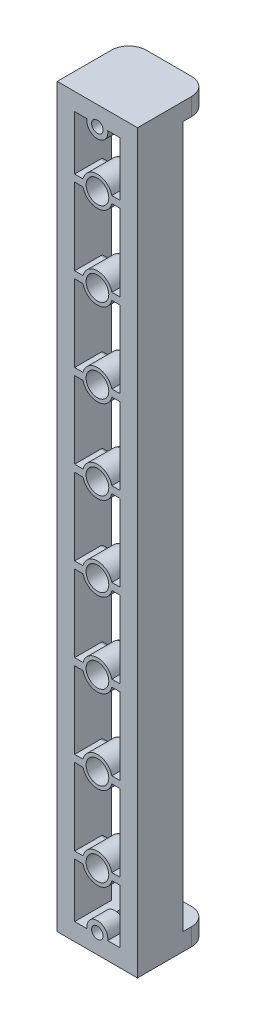
SolidWorks part; units mm, degrees
ref_plane "Front Plane" through (0, 0, 0) normal (0, 0, 1) x (1, 0, 0)
ref_plane "Top Plane" through (0, 0, 0) normal (0, 1, 0) x (1, 0, 0)
ref_plane "Right Plane" through (0, 0, 0) normal (1, 0, 0) x (0, 0, -1)
sketch "Sketch1" plane through (0, 0, 0) normal (0, 0, 1) x (1, 0, 0)
  line L0 (6.5, 100.5) -> (6.5, -100.5)
  line L1 (-11.5, 105.5) -> (11.5, 105.5)
  line L2 (-11.5, 105.5) -> (-11.5, -105.5)
  line L3 (-11.5, -105.5) -> (11.5, -105.5)
  line L4 (11.5, 105.5) -> (11.5, -105.5)
  line L5 (-11.5, 105.5) -> (11.5, -105.5) construction
  line L6 (-11.5, -105.5) -> (11.5, 105.5) construction
  line L7 (-6.5, -100.5) -> (6.5, -100.5)
  line L8 (-6.5, 100.5) -> (-6.5, -100.5)
  line L9 (-6.5, 100.5) -> (6.5, 100.5)
  point P0 (0, 0)
  dimension "D1" = 23
  dimension "D2" = 211
  dimension "D3" = 5
extrude "Boss-Extrude1" add sketch "Sketch1" along normal blind 13
sketch "Sketch7" plane through (0, 0, 13) normal (0, 0, 1) x (1, 0, 0)
  line L0 (0.0237, 87.6593) -> (0.0237, 80.2815) construction
  line L5 (-3.3958, 83) -> (-7.3958, 83)
  line L6 (7.4431, 85) -> (3.4431, 85)
  line L11 (-3.3958, 85) -> (-3.3958, 83)
  line L12 (-7.3958, 85) -> (-3.3958, 85)
  line L13 (3.4431, 85) -> (3.4431, 83)
  line L14 (3.4431, 83) -> (7.4431, 83)
  line L15 (7.4431, 83) -> (7.4431, 85)
  line L16 (-7.3958, 83) -> (-7.3958, 85)
  line L18 (11.5, 105.5) -> (-11.5, 105.5) construction
  circle A0 centre (0.0237, 84) radius 3.25
  circle A1 centre (0.0237, 84) radius 4.25
  point P5 (7.4431, 84)
  dimension "D1" = 6.5
  dimension "D2" = 8.5
  dimension "D3" = 20.5
  dimension "D4" = 4
  dimension "D5" = 2
extrude "Boss-Extrude5" add sketch "Sketch7" against normal blind 8.5
fillet "Fillet4" radius 1 6 edges at (-5.3035, 83, 4.5) (5.3272, 85, 4.5) (-5.3035, 85, 4.5) (0.0237, 88.25, 4.5) (5.3272, 83, 4.5) (0.0237, 79.75, 4.5)
pattern_linear "LPattern7" count 8 spacing 24 along (0, -1, 0) of "Boss-Extrude5", "Fillet4"
sketch "Sketch11" plane through (0, -105.5, 0) normal (0, -1, 0) x (-1, 0, 0)
  line L0 (6.5, -2.0313) -> (6.5, 0)
  line L2 (11.5, 0) -> (-11.5, 0) construction
  line L3 (11.5, -13) -> (11.5, 0) construction
  line L4 (8.5313, 0) -> (6.5, 0)
  line L5 (0, 0) -> (0, -13) construction
  line L6 (11.5, -13) -> (-11.5, -13) construction
  line L7 (-8.5313, 0) -> (-6.5, 0)
  line L8 (-6.5, -2.0313) -> (-6.5, 0)
  arc A0 (6.5, -2.0313) -> (8.5313, 0) centre (6.5, 0) ccw
  arc A1 (-6.5, -2.0313) -> (-8.5313, 0) centre (-6.5, 0) cw
  dimension "D1" = 5
ref_plane "Plane1" through (0, 0, 0) normal (-1, 0, 0) x (0, 0, 1)
ref_plane "Plane2" through (0, 0, 0) normal (0, 1, 0) x (1, 0, 0)
sketch "Sketch15" plane through (0, 105.5, 0) normal (0, 1, 0) x (1, 0, 0)
  line L0 (11.5, 0) -> (-11.5, 0)
  line L4 (11.5, 0) -> (4.4687, 0)
  line L5 (-11.5, 0) -> (-11.5, -13)
  line L6 (-11.5, -13) -> (11.5, -13)
  line L7 (11.5, -13) -> (11.5, 0)
  line L9 (-11.5, 0) -> (-11.5, -13)
  line L10 (-11.5, -13) -> (11.5, -13)
  line L11 (11.5, -13) -> (11.5, 0)
  line L21 (-6.5, 0) -> (-6.5, -2.0313)
  line L25 (-8.5313, 0) -> (-11.5, 0)
  line L26 (6.5, -2.0313) -> (6.5, 0)
  line L27 (6.5, 0) -> (-6.5, 0)
  arc A2 (-8.5313, 0) -> (-6.5, -2.0313) centre (-6.5, 0) ccw
  arc A6 (6.5, -2.0313) -> (4.4687, 0) centre (6.5, 0) ccw
  dimension "D1" = 0
extrude "Boss-Extrude8" add sketch "Sketch15" along normal blind 5
mirror "Mirror5" about plane through (0, 0, 0) normal (0, 1, 0) of "Boss-Extrude8"
sketch "Sketch19" plane through (-11.5, 0, 0) normal (-1, 0, 0) x (0, 0, 1)
  line L0 (13, 105.5) -> (0, 105.5) construction
  line L1 (13, 110.5) -> (13, -110.5) construction
  line L2 (0, 110.5) -> (0, -110.5) construction
  line L3 (0, 110.5) -> (13, 110.5) construction
  line L4 (13, 82.75) -> (0, 82.75) construction
  line L5 (13, 84.75) -> (0, 84.75) construction
  line L6 (0, 98.125) -> (13, 98.125) construction
  line L7 (9.5485, 103.625) -> (3.5485, 103.625)
  line L8 (3.5485, 103.625) -> (3.5485, 98.625)
  line L9 (3.5485, 98.625) -> (9.5485, 103.625)
  line L10 (11.5, 103.625) -> (11.5, 98.625)
  line L11 (11.5, 98.625) -> (5.5, 98.625)
  line L12 (5.5, 98.625) -> (11.5, 103.625)
  line L13 (0, 92.125) -> (13, 92.125) construction
  line L14 (0, 0) -> (13, 0) construction
  line L15 (11.5, 97.625) -> (5.5, 97.625)
  line L16 (11.5, 92.625) -> (11.5, 97.625)
  line L17 (5.5, 97.625) -> (11.5, 92.625)
  line L18 (3.5485, 92.625) -> (3.5485, 97.625)
  line L19 (9.5485, 92.625) -> (3.5485, 92.625)
  line L20 (3.5485, 97.625) -> (9.5485, 92.625)
  line L21 (11.5, 91.625) -> (11.5, 86.625)
  line L22 (5.5, 86.625) -> (11.5, 91.625)
  line L23 (11.5, 86.625) -> (5.5, 86.625)
  line L24 (9.5485, 91.625) -> (3.5485, 91.625)
  line L25 (3.5485, 86.625) -> (9.5485, 91.625)
  line L26 (3.5485, 91.625) -> (3.5485, 86.625)
  dimension "D1" = 5
  dimension "D2" = 5
  dimension "D3" = 2
  dimension "D4" = 1.2493
  dimension "D5" = 1.5
  dimension "D6" = 0.5
  dimension "D7" = 1.875
  dimension "D8" = 6
  dimension "D9" = 0.5
extrude "Cut-Extrude7" [suppressed] cut sketch "Sketch19" against normal blind 5
pattern_linear "LPattern10" [suppressed] count 9 spacing 23.8
ref_plane "Plane3" through (0, 0, 0) normal (-1, 0, 0) x (0, 0, 1)
mirror "Mirror7" [suppressed] about plane through (0, 0, 0) normal (-1, 0, 0)
sketch "Sketch22" plane through (0, 0, 0) normal (0, 0, -1) x (-1, 0, 0)
  line L0 (11.5, 110.5) -> (11.5, -110.5) construction
  line L1 (-11.5, 110.5) -> (11.5, 110.5)
  line L2 (-11.5, 110.5) -> (-11.5, 105.5)
  line L3 (-11.5, 105.5) -> (11.5, 105.5)
  line L4 (11.5, 110.5) -> (11.5, 105.5)
  line L6 (-11.5, -110.5) -> (11.5, -110.5)
  line L7 (-11.5, -110.5) -> (-11.5, -105.5)
  line L8 (-11.5, -105.5) -> (11.5, -105.5)
  line L9 (11.5, -110.5) -> (11.5, -105.5)
  dimension "D1" = 5
  dimension "D2" = 5
extrude "Cut-Extrude9" cut sketch "Sketch22" against normal through all
sketch "Sketch21" plane through (0, 0, 13) normal (0, 0, 1) x (1, 0, 0)
  line L1 (6.5, 100.5) -> (-6.5, 100.5) construction
  line L6 (-4.7323, 0) -> (3.9666, 0) construction
  line L11 (-2.5, 100.5) -> (2.5, 100.5)
  line L12 (-2.5, 100.5) -> (-2.5, 103.5)
  line L13 (-2.5, 103.5) -> (2.5, 103.5)
  line L14 (2.5, 100.5) -> (2.5, 103.5)
  line L15 (11.5, 105.5) -> (-11.5, 105.5) construction
  line L16 (-2.5, -103.5) -> (2.5, -103.5)
  line L17 (2.5, -100.5) -> (2.5, -103.5)
  line L18 (-2.5, -100.5) -> (2.5, -100.5)
  line L19 (-2.5, -100.5) -> (-2.5, -103.5)
  point P18 (0, 105.5)
  point P19 (0, 103.5)
  dimension "D3" = 3
  dimension "D4" = 5
extrude "Cut-Extrude8" [suppressed] cut sketch "Sketch21" against normal blind 5
fillet "Fillet7" [suppressed] radius 1
sketch "Sketch23" plane through (0, 0, 0) normal (0, 0, -1) x (-1, 0, 0)
  line L0 (11.5, 105.5) -> (11.5, -105.5) construction
  line L1 (-11.5, 105.5) -> (11.5, 105.5)
  line L2 (-11.5, 105.5) -> (-11.5, 100.5)
  line L3 (-11.5, 100.5) -> (11.5, 100.5)
  line L4 (11.5, 105.5) -> (11.5, 100.5)
  line L5 (-6.5, 100.5) -> (6.5, 100.5) construction
  line L6 (6.5, -100.5) -> (-6.5, -100.5) construction
  line L7 (-11.5, -105.5) -> (11.5, -105.5)
  line L8 (-11.5, -105.5) -> (-11.5, -100.5)
  line L9 (-11.5, -100.5) -> (11.5, -100.5)
  line L10 (11.5, -105.5) -> (11.5, -100.5)
extrude "Boss-Extrude9" add sketch "Sketch23" along normal blind 7.5
fillet "Fillet8" radius 5 4 edges at (11.5, 103, -7.5) (-11.5, 103, -7.5) (-11.5, -103, -7.5) (11.5, -103, -7.5)
sketch "Sketch25" plane through (0, -105.5, 0) normal (0, -1, 0) x (1, 0, 0)
  line L4 (-11.5, 13) -> (-11.5, -2.5) construction
  line L5 (-11.5, 13) -> (11.5, 13) construction
  line L6 (-9, -0.5) -> (-6, -0.5)
  line L7 (-6, -0.5) -> (-6, 2.5)
  line L8 (0, 2.725) -> (0, -1.8067) construction
  line L9 (6, -0.5) -> (6, 2.5)
  line L10 (9, -0.5) -> (6, -0.5)
  arc A0 (-6, 2.5) -> (-9, -0.5) centre (-6, -0.5) ccw
  arc A1 (6, 2.5) -> (9, -0.5) centre (6, -0.5) cw
  dimension "D1" = 13.5
  dimension "D2" = 5.5
  dimension "D3" = 3
extrude "Cut-Extrude11" cut sketch "Sketch25" against normal up to surface (201 mm away) from surface at -5 up to face at (0, 100.5, 0.3929) starting at face at (0, -100.5, 0.3929)
sketch "Sketch26" plane through (0, 0, 13) normal (0, 0, 1) x (1, 0, 0)
  line L0 (0, 100) -> (0, -100) construction
  circle A0 centre (0, -100) radius 3
  circle A1 centre (0, 100) radius 3
  point P4 (0, 0)
  dimension "D2" = 6
  dimension "D1" = 200
extrude "Boss-Extrude10" add sketch "Sketch26" against normal blind 5
sketch "Sketch27" plane through (0, 0, 13) normal (0, 0, 1) x (1, 0, 0)
  circle A0 centre (0, -100) radius 1.65
  circle A1 centre (0, 100) radius 1.65
  dimension "D1" = 3.3
extrude "Cut-Extrude12" cut sketch "Sketch27" against normal through all
sketch "Sketch28" plane through (0, 0, 8) normal (0, 0, -1) x (-1, 0, 0)
  circle A0 centre (0, 100) radius 3
  circle A1 centre (0, -100) radius 3
  dimension "D1" = 6
  dimension "D2" = 6
extrude "Cut-Extrude13" cut sketch "Sketch28" along normal blind 24
